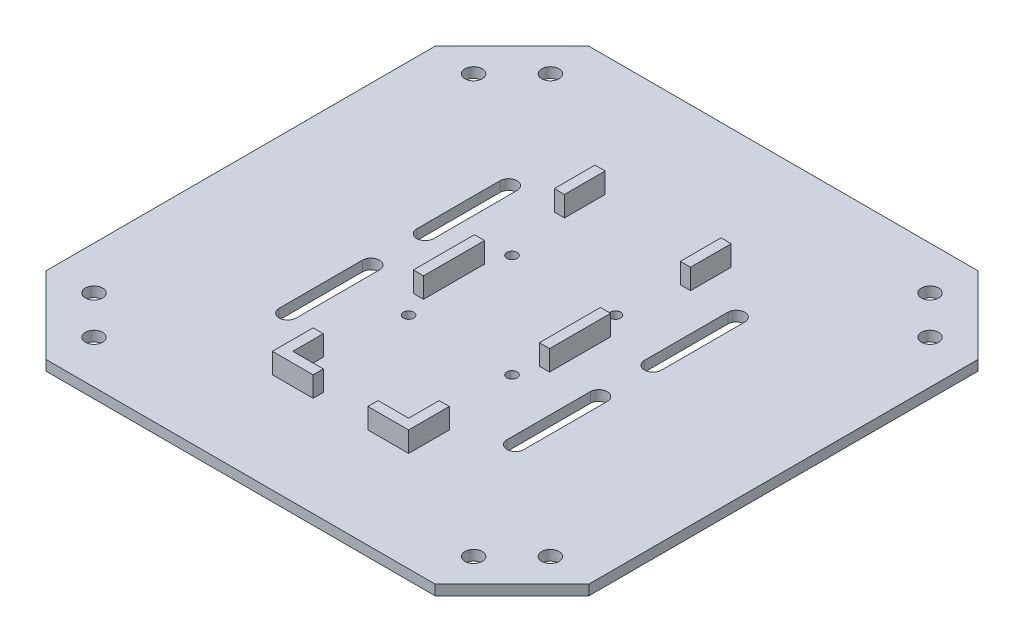
SolidWorks part; units mm, degrees
material "Custom Plastic"
ref_plane "Front Plane" through (0, 0, 0) normal (0, 0, 1) x (1, 0, 0)
ref_plane "Top Plane" through (0, 0, 0) normal (0, 1, 0) x (1, 0, 0)
ref_plane "Right Plane" through (0, 0, 0) normal (1, 0, 0) x (0, 0, -1)
sketch "Sketch1" plane through (0, 0, 0) normal (0, 1, 0) x (1, 0, 0)
  line L1 (80, 80) -> (-80, 80)
  line L2 (80, 80) -> (80, -80)
  line L3 (80, -80) -> (-80, -80)
  line L4 (-80, 80) -> (-80, -80)
  point P0 (0, 0)
  dimension "D1" = 160
  dimension "D2" = 80
  dimension "D3" = 80
extrude "Boss-Extrude1" add sketch "Sketch1" against normal blind 3
sketch "Sketch6" plane through (0, 0, 0) normal (0, 1, 0) x (1, 0, 0)
  line L0 (-80, -57.3726) -> (-57.3726, -80)
  line L1 (-80, 80) -> (-80, -80) construction
  line L2 (-80, -80) -> (80, -80) construction
  line L3 (-57.3726, -80) -> (-80, -80)
  line L4 (-80, -80) -> (-80, -57.3726)
  dimension "D1" = 45
  dimension "D2" = 32
extrude "Cut-Extrude2" cut sketch "Sketch6" against normal up to next
sketch "Sketch2" plane through (0, 0, 0) normal (0, 1, 0) x (1, 0, 0)
  line L0 (-67.2721, -55.9584) -> (-55.9584, -67.2721) construction
  line L1 (-68.6863, -68.6863) -> (-61.6152, -61.6152) construction
  line L5 (-57.3726, -80) -> (-80, -57.3726) construction
  circle A0 centre (-67.2721, -55.9584) radius 2.55
  circle A1 centre (-55.9584, -67.2721) radius 2.55
  dimension "D1" = 16
  dimension "D2" = 10
  dimension "D3" = 5.1
extrude "Cut-Extrude1" cut sketch "Sketch2" against normal up to next
mirror "Mirror2" about plane through (0, 0, 0) normal (1, 0, 0) of "Cut-Extrude2", "Cut-Extrude1" second plane through (0, 0, 0) second plane normal (0, 0, 1)
sketch "Sketch10" plane through (0, 0, 0) normal (0, 1, 0) x (1, 0, 0)
  line L0 (-62, 26.5) -> (-62, 12)
  line L1 (-62, 12) -> (-58, 12)
  line L2 (-58, 12) -> (-58, 22.5)
  line L3 (-58, 22.5) -> (-40, 22.5)
  line L4 (-40, 22.5) -> (-40, 26.5)
  line L5 (-40, 26.5) -> (-62, 26.5)
  line L6 (-62, -12) -> (-58, -12)
  line L7 (-58, -12) -> (-58, -22.5)
  line L8 (-58, -22.5) -> (-40, -22.5)
  line L9 (-40, -22.5) -> (-40, -26.5)
  line L10 (-40, -26.5) -> (-62, -26.5)
  line L11 (-62, -26.5) -> (-62, -12)
  line L12 (-49, 22.5) -> (-49, -22.5) construction
  line L13 (-49, 0) -> (0, 0) construction
  line L16 (-80, 57.3726) -> (-80, -57.3726) construction
  dimension "D1" = 45
  dimension "D2" = 4
  dimension "D3" = 18
  dimension "D4" = 22
  dimension "D5" = 24
sketch "Sketch11" plane through (0, 0, 0) normal (0, 1, 0) x (1, 0, 0)
  line L1 (-15.25, 15.25) -> (15.25, 15.25) construction
  line L2 (-15.25, 15.25) -> (-15.25, -15.25) construction
  line L3 (-15.25, -15.25) -> (15.25, -15.25) construction
  line L4 (15.25, 15.25) -> (15.25, -15.25) construction
  line L5 (-15.25, 15.25) -> (15.25, -15.25) construction
  line L6 (-15.25, -15.25) -> (15.25, 15.25) construction
  circle A0 centre (-15.25, 15.25) radius 1.525
  circle A1 centre (15.25, 15.25) radius 1.525
  circle A2 centre (15.25, -15.25) radius 1.525
  circle A3 centre (-15.25, -15.25) radius 1.525
  point P0 (0, 0)
  dimension "D2" = 3.05
  dimension "D1" = 30.5
extrude "Cut-Extrude3" cut sketch "Sketch11" against normal up to next
sketch "Sketch12" plane through (0, 0, 0) normal (0, 1, 0) x (1, 0, 0)
  line L0 (-17.075, -47.55) -> (-8.075, -47.55)
  line L1 (17.075, 47.55) -> (-17.075, 47.55) construction
  line L2 (17.075, 47.55) -> (17.075, -47.55) construction
  line L3 (17.075, -47.55) -> (-17.075, -47.55) construction
  line L4 (-17.075, 47.55) -> (-17.075, -47.55) construction
  line L5 (17.075, 47.55) -> (-17.075, -47.55) construction
  line L6 (17.075, -47.55) -> (-17.075, 47.55) construction
  line L7 (-8.075, -47.55) -> (-8.075, -50.55)
  line L8 (-8.075, -50.55) -> (-20.075, -50.55)
  line L9 (-20.075, -50.55) -> (-20.075, -38.55)
  line L10 (-20.075, -38.55) -> (-17.075, -38.55)
  line L11 (-17.075, -38.55) -> (-17.075, -47.55)
  line L13 (-20.075, 44.55) -> (-20.075, 32.55)
  line L14 (-20.075, 32.55) -> (-17.075, 32.55)
  line L16 (-17.075, 9) -> (-20.075, 9)
  line L17 (-20.075, 9) -> (-20.075, -9)
  line L18 (-20.075, -9) -> (-17.075, -9)
  line L19 (-17.075, -9) -> (-17.075, 9)
  line L20 (-20.075, 0) -> (-17.075, 0) construction
  line L21 (-17.075, 32.55) -> (-17.075, 44.55)
  line L22 (-17.075, 44.55) -> (-20.075, 44.55)
  point P0 (0, 0)
  dimension "D1" = 95.1
  dimension "D2" = 34.15
  dimension "D3" = 3
  dimension "D4" = 9
  dimension "D5" = 18
  dimension "D6" = 12
  dimension "D7" = 3
extrude "Boss-Extrude2" add sketch "Sketch12" along normal blind 6
mirror "Mirror3" about plane through (0, 0, 0) normal (1, 0, 0) of "Boss-Extrude2"
sketch "Sketch13" plane through (0, 0, 0) normal (0, 1, 0) x (1, 0, 0)
  line L0 (-18.575, 32.55) -> (-18.575, 9) construction
  line L1 (-20.075, 32.55) -> (-17.075, 32.55) construction
  line L2 (-17.075, 9) -> (-20.075, 9) construction
  line L3 (-18.575, 20.775) -> (-33.575, 20.775) construction
  line L4 (-33.575, 32.55) -> (-33.575, 8) construction
  line L5 (-31.075, 32.55) -> (-31.075, 8)
  line L6 (-36.075, 32.55) -> (-36.075, 8)
  arc A0 (-31.075, 32.55) -> (-36.075, 32.55) centre (-33.575, 32.55) ccw
  arc A1 (-36.075, 8) -> (-31.075, 8) centre (-33.575, 8) ccw
  point P10 (-33.575, 20.275)
  dimension "D1" = 15
  dimension "D2" = 5
  dimension "D3" = 24.55
extrude "Cut-Extrude4" cut sketch "Sketch13" against normal up to next
mirror "Mirror4" about plane through (0, 0, 0) normal (1, 0, 0) of "Cut-Extrude4" second plane through (0, 0, 0) second plane normal (0, 0, 1)
equation "\"body_length\"= 160"
equation "\"D1@Sketch1\"=\"body_length\""
equation "\"D2@Sketch1\"=\"body_length\"/2"
equation "\"D3@Sketch1\"=\"body_length\"/2"
